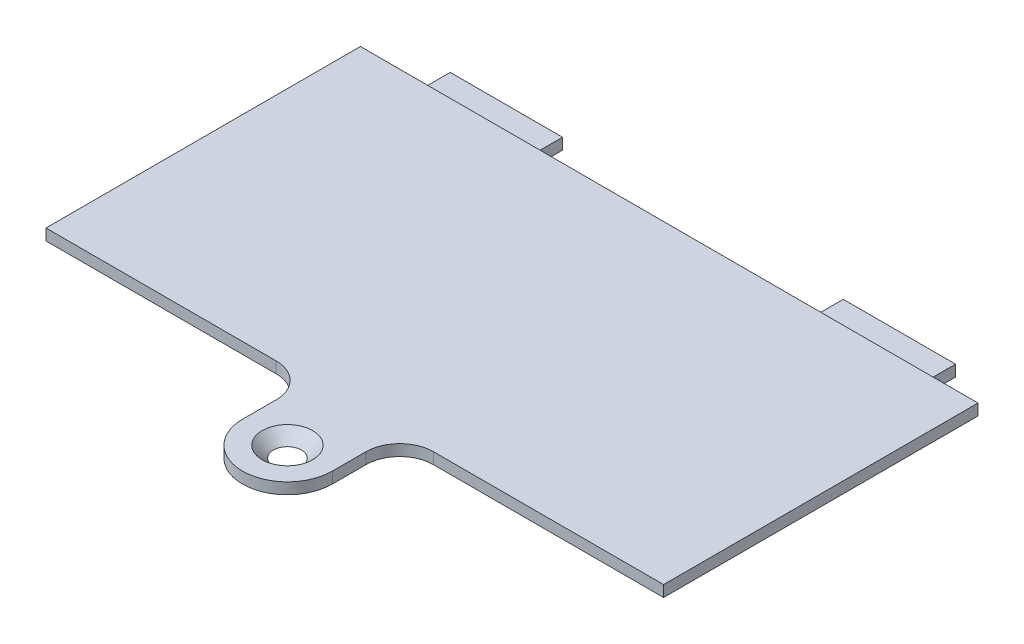
SolidWorks part; units mm, degrees
ref_plane "Front Plane" through (0, 0, 0) normal (0, 0, 1) x (1, 0, 0)
ref_plane "Top Plane" through (0, 0, 0) normal (0, 1, 0) x (1, 0, 0)
ref_plane "Right Plane" through (0, 0, 0) normal (1, 0, 0) x (0, 0, -1)
sketch "Sketch1" plane through (0, 0, 0) normal (0, 1, 0) x (1, 0, 0)
  line L0 (23.5, -6) -> (23.5, 0)
  line L1 (0, 0) -> (55, 0)
  line L2 (0, 0) -> (0, 28)
  line L3 (0, 28) -> (55, 28)
  line L4 (55, 0) -> (55, 28)
  line L5 (23.5, 0) -> (0, 0)
  line L6 (31.5, -6) -> (31.5, 0)
  line L7 (31.5, 0) -> (55, 0)
  circle A0 centre (27.5, -6) radius 4
  circle A1 centre (27.5, -6) radius 1.25
  dimension "D3" = 8
  dimension "D4" = 6
  dimension "D1" = 55
  dimension "D2" = 28
extrude "Boss-Extrude1" add sketch "Sketch1" along normal blind 1 contours L1 L4 L3 L2 | A0 L6 L1 L0 | A0 A1 region at (27.5, 0, 1.5686) region at (27.5, 0, 2.1131) region at (27.5, 0, -14)
fillet "Fillet1" radius 3 2 edges at (31.5, 0.5, 0) (23.5, 0.5, 0)
sketch "Sketch2" plane through (0, 0, 0) normal (0, -1, 0) x (-1, 0, 0)
  line L0 (0, 0) -> (0, 28) construction
  line L1 (-5, 26) -> (-15, 26)
  line L2 (-5, 26) -> (-5, 31)
  line L3 (-5, 31) -> (-15, 31)
  line L4 (-15, 26) -> (-15, 31)
  line L5 (-40, 26) -> (-50, 26)
  line L6 (-40, 26) -> (-40, 31)
  line L7 (-40, 31) -> (-50, 31)
  line L8 (-50, 26) -> (-50, 31)
  line L9 (-55, 0) -> (-55, 28) construction
  line L10 (0, 28) -> (-55, 28) construction
  dimension "D1" = 5
  dimension "D2" = 10
  dimension "D3" = 5
  dimension "D4" = 10
  dimension "D5" = 2
  dimension "D6" = 2
  dimension "D7" = 5
  dimension "D8" = 5
extrude "Boss-Extrude2" add sketch "Sketch2" along normal blind 1
chamfer "Chamfer1" distance 1 angle 45 2 edges at (45, 0, -26) (10, 0, -26)
chamfer "Chamfer2" distance 1 angle 45 1 edges at (27.5, 1, 7.25)
